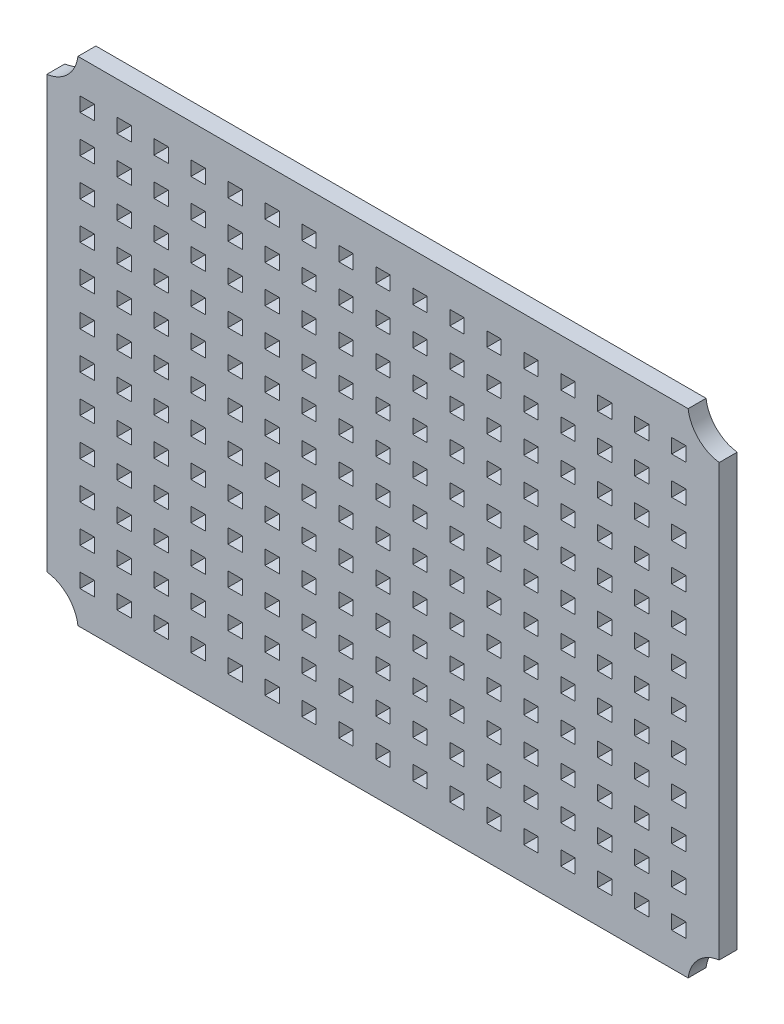
SolidWorks part; units mm, degrees
ref_plane "Plano frontal" through (0, 0, 0) normal (0, 0, 1) x (1, 0, 0)
ref_plane "Plano superior" through (0, 0, 0) normal (0, 1, 0) x (1, 0, 0)
ref_plane "Plano direito" through (0, 0, 0) normal (1, 0, 0) x (0, 0, -1)
sketch "Esboço1" plane through (0, 0, 0) normal (0, 0, 1) x (1, 0, 0)
  line L0 (-85, 70) -> (85, 70)
  line L1 (95, 60) -> (95, -60)
  line L2 (85, -70) -> (-85, -70)
  line L3 (-95, -60) -> (-95, 60)
  arc A0 (-95, 60) -> (-85, 70) centre (-95, 70) ccw
  arc A1 (85, 70) -> (95, 60) centre (95, 70) ccw
  arc A2 (95, -60) -> (85, -70) centre (95, -70) ccw
  arc A3 (-85, -70) -> (-95, -60) centre (-95, -70) ccw
extrude "Ressalto-extrusão1" add sketch "Esboço1" along normal blind 5
sketch "Esboço2" plane through (0, 0, 5) normal (0, 0, 1) x (1, 0, 0)
  line L1 (-87.9289, 62.9289) -> (87.9289, 62.9289)
  line L2 (-87.9289, 62.9289) -> (-87.9289, -62.9289)
  line L3 (-87.9289, -62.9289) -> (87.9289, -62.9289)
  line L4 (87.9289, 62.9289) -> (87.9289, -62.9289)
  line L5 (-87.9289, 62.9289) -> (87.9289, -62.9289) construction
  line L6 (-87.9289, -62.9289) -> (87.9289, 62.9289) construction
  arc A0 (95, -60) -> (85, -70) centre (95, -70) ccw construction
  point P0 (0, 0)
sketch "Esboço3" plane through (0, 0, 5) normal (0, 0, 1) x (1, 0, 0)
  line L0 (-74.1875, 55.5) -> (-70.1875, 55.5)
  line L7 (-70.1875, 59.5) -> (-70.1875, 55.5)
  line L8 (-74.1875, 59.5) -> (-70.1875, 59.5)
  line L9 (-74.1875, 59.5) -> (-74.1875, 55.5)
  line L10 (-84.5, 59.5) -> (-80.5, 59.5)
  line L11 (-84.5, 59.5) -> (-84.5, 55.5)
  line L12 (-84.5, 55.5) -> (-80.5, 55.5)
  line L13 (-80.5, 59.5) -> (-80.5, 55.5)
  line L14 (-84.5, 59.5) -> (-80.5, 55.5) construction
  line L15 (-84.5, 55.5) -> (-80.5, 59.5) construction
  line L16 (-63.875, 55.5) -> (-59.875, 55.5)
  line L17 (-59.875, 59.5) -> (-59.875, 55.5)
  line L18 (-63.875, 59.5) -> (-59.875, 59.5)
  line L19 (-63.875, 59.5) -> (-63.875, 55.5)
  line L20 (-53.5625, 55.5) -> (-49.5625, 55.5)
  line L21 (-49.5625, 59.5) -> (-49.5625, 55.5)
  line L22 (-53.5625, 59.5) -> (-49.5625, 59.5)
  line L23 (-53.5625, 59.5) -> (-53.5625, 55.5)
  line L24 (-43.25, 55.5) -> (-39.25, 55.5)
  line L25 (-39.25, 59.5) -> (-39.25, 55.5)
  line L26 (-43.25, 59.5) -> (-39.25, 59.5)
  line L27 (-43.25, 59.5) -> (-43.25, 55.5)
  line L28 (-32.9375, 55.5) -> (-28.9375, 55.5)
  line L29 (-28.9375, 59.5) -> (-28.9375, 55.5)
  line L30 (-32.9375, 59.5) -> (-28.9375, 59.5)
  line L31 (-32.9375, 59.5) -> (-32.9375, 55.5)
  line L32 (-22.625, 55.5) -> (-18.625, 55.5)
  line L33 (-18.625, 59.5) -> (-18.625, 55.5)
  line L34 (-22.625, 59.5) -> (-18.625, 59.5)
  line L35 (-22.625, 59.5) -> (-22.625, 55.5)
  line L36 (-12.3125, 55.5) -> (-8.3125, 55.5)
  line L37 (-8.3125, 59.5) -> (-8.3125, 55.5)
  line L38 (-12.3125, 59.5) -> (-8.3125, 59.5)
  line L39 (-12.3125, 59.5) -> (-12.3125, 55.5)
  line L40 (-2, 55.5) -> (2, 55.5)
  line L41 (2, 59.5) -> (2, 55.5)
  line L42 (-2, 59.5) -> (2, 59.5)
  line L43 (-2, 59.5) -> (-2, 55.5)
  line L44 (8.3125, 55.5) -> (12.3125, 55.5)
  line L45 (12.3125, 59.5) -> (12.3125, 55.5)
  line L46 (8.3125, 59.5) -> (12.3125, 59.5)
  line L47 (8.3125, 59.5) -> (8.3125, 55.5)
  line L48 (18.625, 55.5) -> (22.625, 55.5)
  line L49 (22.625, 59.5) -> (22.625, 55.5)
  line L50 (18.625, 59.5) -> (22.625, 59.5)
  line L51 (18.625, 59.5) -> (18.625, 55.5)
  line L52 (28.9375, 55.5) -> (32.9375, 55.5)
  line L53 (32.9375, 59.5) -> (32.9375, 55.5)
  line L54 (28.9375, 59.5) -> (32.9375, 59.5)
  line L55 (28.9375, 59.5) -> (28.9375, 55.5)
  line L56 (39.25, 55.5) -> (43.25, 55.5)
  line L57 (43.25, 59.5) -> (43.25, 55.5)
  line L58 (39.25, 59.5) -> (43.25, 59.5)
  line L59 (39.25, 59.5) -> (39.25, 55.5)
  line L60 (49.5625, 55.5) -> (53.5625, 55.5)
  line L61 (53.5625, 59.5) -> (53.5625, 55.5)
  line L62 (49.5625, 59.5) -> (53.5625, 59.5)
  line L63 (49.5625, 59.5) -> (49.5625, 55.5)
  line L64 (59.875, 55.5) -> (63.875, 55.5)
  line L65 (63.875, 59.5) -> (63.875, 55.5)
  line L66 (59.875, 59.5) -> (63.875, 59.5)
  line L67 (59.875, 59.5) -> (59.875, 55.5)
  line L68 (70.1875, 55.5) -> (74.1875, 55.5)
  line L69 (74.1875, 59.5) -> (74.1875, 55.5)
  line L70 (70.1875, 59.5) -> (74.1875, 59.5)
  line L71 (70.1875, 59.5) -> (70.1875, 55.5)
  line L72 (80.5, 55.5) -> (84.5, 55.5)
  line L73 (84.5, 59.5) -> (84.5, 55.5)
  line L74 (80.5, 59.5) -> (84.5, 59.5)
  line L75 (80.5, 59.5) -> (80.5, 55.5)
  line L76 (-74.1875, 45.0455) -> (-70.1875, 45.0455)
  line L77 (-70.1875, 49.0455) -> (-70.1875, 45.0455)
  line L78 (-74.1875, 49.0455) -> (-70.1875, 49.0455)
  line L79 (-74.1875, 49.0455) -> (-74.1875, 45.0455)
  line L80 (-63.875, 45.0455) -> (-59.875, 45.0455)
  line L81 (-59.875, 49.0455) -> (-59.875, 45.0455)
  line L82 (-63.875, 49.0455) -> (-59.875, 49.0455)
  line L83 (-63.875, 49.0455) -> (-63.875, 45.0455)
  line L84 (-53.5625, 45.0455) -> (-49.5625, 45.0455)
  line L85 (-49.5625, 49.0455) -> (-49.5625, 45.0455)
  line L86 (-53.5625, 49.0455) -> (-49.5625, 49.0455)
  line L87 (-53.5625, 49.0455) -> (-53.5625, 45.0455)
  line L88 (-43.25, 45.0455) -> (-39.25, 45.0455)
  line L89 (-39.25, 49.0455) -> (-39.25, 45.0455)
  line L90 (-43.25, 49.0455) -> (-39.25, 49.0455)
  line L91 (-43.25, 49.0455) -> (-43.25, 45.0455)
  line L92 (-32.9375, 45.0455) -> (-28.9375, 45.0455)
  line L93 (-28.9375, 49.0455) -> (-28.9375, 45.0455)
  line L94 (-32.9375, 49.0455) -> (-28.9375, 49.0455)
  line L95 (-32.9375, 49.0455) -> (-32.9375, 45.0455)
  line L96 (-22.625, 45.0455) -> (-18.625, 45.0455)
  line L97 (-18.625, 49.0455) -> (-18.625, 45.0455)
  line L98 (-22.625, 49.0455) -> (-18.625, 49.0455)
  line L99 (-22.625, 49.0455) -> (-22.625, 45.0455)
  line L100 (-12.3125, 45.0455) -> (-8.3125, 45.0455)
  line L101 (-8.3125, 49.0455) -> (-8.3125, 45.0455)
  line L102 (-12.3125, 49.0455) -> (-8.3125, 49.0455)
  line L103 (-12.3125, 49.0455) -> (-12.3125, 45.0455)
  line L104 (-2, 45.0455) -> (2, 45.0455)
  line L105 (2, 49.0455) -> (2, 45.0455)
  line L106 (-2, 49.0455) -> (2, 49.0455)
  line L107 (-2, 49.0455) -> (-2, 45.0455)
  line L108 (8.3125, 45.0455) -> (12.3125, 45.0455)
  line L109 (12.3125, 49.0455) -> (12.3125, 45.0455)
  line L110 (8.3125, 49.0455) -> (12.3125, 49.0455)
  line L111 (8.3125, 49.0455) -> (8.3125, 45.0455)
  line L112 (18.625, 45.0455) -> (22.625, 45.0455)
  line L113 (22.625, 49.0455) -> (22.625, 45.0455)
  line L114 (18.625, 49.0455) -> (22.625, 49.0455)
  line L115 (18.625, 49.0455) -> (18.625, 45.0455)
  line L116 (28.9375, 45.0455) -> (32.9375, 45.0455)
  line L117 (32.9375, 49.0455) -> (32.9375, 45.0455)
  line L118 (28.9375, 49.0455) -> (32.9375, 49.0455)
  line L119 (28.9375, 49.0455) -> (28.9375, 45.0455)
  line L120 (39.25, 45.0455) -> (43.25, 45.0455)
  line L121 (43.25, 49.0455) -> (43.25, 45.0455)
  line L122 (39.25, 49.0455) -> (43.25, 49.0455)
  line L123 (39.25, 49.0455) -> (39.25, 45.0455)
  line L124 (49.5625, 45.0455) -> (53.5625, 45.0455)
  line L125 (53.5625, 49.0455) -> (53.5625, 45.0455)
  line L126 (49.5625, 49.0455) -> (53.5625, 49.0455)
  line L127 (49.5625, 49.0455) -> (49.5625, 45.0455)
  line L128 (59.875, 45.0455) -> (63.875, 45.0455)
  line L129 (63.875, 49.0455) -> (63.875, 45.0455)
  line L130 (59.875, 49.0455) -> (63.875, 49.0455)
  line L131 (59.875, 49.0455) -> (59.875, 45.0455)
  line L132 (70.1875, 45.0455) -> (74.1875, 45.0455)
  line L133 (74.1875, 49.0455) -> (74.1875, 45.0455)
  line L134 (70.1875, 49.0455) -> (74.1875, 49.0455)
  line L135 (70.1875, 49.0455) -> (70.1875, 45.0455)
  line L136 (80.5, 45.0455) -> (84.5, 45.0455)
  line L137 (84.5, 49.0455) -> (84.5, 45.0455)
  line L138 (80.5, 49.0455) -> (84.5, 49.0455)
  line L139 (80.5, 49.0455) -> (80.5, 45.0455)
  line L140 (-74.1875, 34.591) -> (-70.1875, 34.591)
  line L141 (-70.1875, 38.591) -> (-70.1875, 34.591)
  line L142 (-74.1875, 38.591) -> (-70.1875, 38.591)
  line L143 (-74.1875, 38.591) -> (-74.1875, 34.591)
  line L144 (-63.875, 34.591) -> (-59.875, 34.591)
  line L145 (-59.875, 38.591) -> (-59.875, 34.591)
  line L146 (-63.875, 38.591) -> (-59.875, 38.591)
  line L147 (-63.875, 38.591) -> (-63.875, 34.591)
  line L148 (-53.5625, 34.591) -> (-49.5625, 34.591)
  line L149 (-49.5625, 38.591) -> (-49.5625, 34.591)
  line L150 (-53.5625, 38.591) -> (-49.5625, 38.591)
  line L151 (-53.5625, 38.591) -> (-53.5625, 34.591)
  line L152 (-43.25, 34.591) -> (-39.25, 34.591)
  line L153 (-39.25, 38.591) -> (-39.25, 34.591)
  line L154 (-43.25, 38.591) -> (-39.25, 38.591)
  line L155 (-43.25, 38.591) -> (-43.25, 34.591)
  line L156 (-32.9375, 34.591) -> (-28.9375, 34.591)
  line L157 (-28.9375, 38.591) -> (-28.9375, 34.591)
  line L158 (-32.9375, 38.591) -> (-28.9375, 38.591)
  line L159 (-32.9375, 38.591) -> (-32.9375, 34.591)
  line L160 (-22.625, 34.591) -> (-18.625, 34.591)
  line L161 (-18.625, 38.591) -> (-18.625, 34.591)
  line L162 (-22.625, 38.591) -> (-18.625, 38.591)
  line L163 (-22.625, 38.591) -> (-22.625, 34.591)
  line L164 (-12.3125, 34.591) -> (-8.3125, 34.591)
  line L165 (-8.3125, 38.591) -> (-8.3125, 34.591)
  line L166 (-12.3125, 38.591) -> (-8.3125, 38.591)
  line L167 (-12.3125, 38.591) -> (-12.3125, 34.591)
  line L168 (-2, 34.591) -> (2, 34.591)
  line L169 (2, 38.591) -> (2, 34.591)
  line L170 (-2, 38.591) -> (2, 38.591)
  line L171 (-2, 38.591) -> (-2, 34.591)
  line L172 (8.3125, 34.591) -> (12.3125, 34.591)
  line L173 (12.3125, 38.591) -> (12.3125, 34.591)
  line L174 (8.3125, 38.591) -> (12.3125, 38.591)
  line L175 (8.3125, 38.591) -> (8.3125, 34.591)
  line L176 (18.625, 34.591) -> (22.625, 34.591)
  line L177 (22.625, 38.591) -> (22.625, 34.591)
  line L178 (18.625, 38.591) -> (22.625, 38.591)
  line L179 (18.625, 38.591) -> (18.625, 34.591)
  line L180 (28.9375, 34.591) -> (32.9375, 34.591)
  line L181 (32.9375, 38.591) -> (32.9375, 34.591)
  line L182 (28.9375, 38.591) -> (32.9375, 38.591)
  line L183 (28.9375, 38.591) -> (28.9375, 34.591)
  line L184 (39.25, 34.591) -> (43.25, 34.591)
  line L185 (43.25, 38.591) -> (43.25, 34.591)
  line L186 (39.25, 38.591) -> (43.25, 38.591)
  line L187 (39.25, 38.591) -> (39.25, 34.591)
  line L188 (49.5625, 34.591) -> (53.5625, 34.591)
  line L189 (53.5625, 38.591) -> (53.5625, 34.591)
  line L190 (49.5625, 38.591) -> (53.5625, 38.591)
  line L191 (49.5625, 38.591) -> (49.5625, 34.591)
  line L192 (59.875, 34.591) -> (63.875, 34.591)
  line L193 (63.875, 38.591) -> (63.875, 34.591)
  line L194 (59.875, 38.591) -> (63.875, 38.591)
  line L195 (59.875, 38.591) -> (59.875, 34.591)
  line L196 (70.1875, 34.591) -> (74.1875, 34.591)
  line L197 (74.1875, 38.591) -> (74.1875, 34.591)
  line L198 (70.1875, 38.591) -> (74.1875, 38.591)
  line L199 (70.1875, 38.591) -> (70.1875, 34.591)
  line L200 (80.5, 34.591) -> (84.5, 34.591)
  line L201 (84.5, 38.591) -> (84.5, 34.591)
  line L202 (80.5, 38.591) -> (84.5, 38.591)
  line L203 (80.5, 38.591) -> (80.5, 34.591)
  line L204 (-74.1875, 24.1365) -> (-70.1875, 24.1365)
  line L205 (-70.1875, 28.1365) -> (-70.1875, 24.1365)
  line L206 (-74.1875, 28.1365) -> (-70.1875, 28.1365)
  line L207 (-74.1875, 28.1365) -> (-74.1875, 24.1365)
  line L208 (-63.875, 24.1365) -> (-59.875, 24.1365)
  line L209 (-59.875, 28.1365) -> (-59.875, 24.1365)
  line L210 (-63.875, 28.1365) -> (-59.875, 28.1365)
  line L211 (-63.875, 28.1365) -> (-63.875, 24.1365)
  line L212 (-53.5625, 24.1365) -> (-49.5625, 24.1365)
  line L213 (-49.5625, 28.1365) -> (-49.5625, 24.1365)
  line L214 (-53.5625, 28.1365) -> (-49.5625, 28.1365)
  line L215 (-53.5625, 28.1365) -> (-53.5625, 24.1365)
  line L216 (-43.25, 24.1365) -> (-39.25, 24.1365)
  line L217 (-39.25, 28.1365) -> (-39.25, 24.1365)
  line L218 (-43.25, 28.1365) -> (-39.25, 28.1365)
  line L219 (-43.25, 28.1365) -> (-43.25, 24.1365)
  line L220 (-32.9375, 24.1365) -> (-28.9375, 24.1365)
  line L221 (-28.9375, 28.1365) -> (-28.9375, 24.1365)
  line L222 (-32.9375, 28.1365) -> (-28.9375, 28.1365)
  line L223 (-32.9375, 28.1365) -> (-32.9375, 24.1365)
  line L224 (-22.625, 24.1365) -> (-18.625, 24.1365)
  line L225 (-18.625, 28.1365) -> (-18.625, 24.1365)
  line L226 (-22.625, 28.1365) -> (-18.625, 28.1365)
  line L227 (-22.625, 28.1365) -> (-22.625, 24.1365)
  line L228 (-12.3125, 24.1365) -> (-8.3125, 24.1365)
  line L229 (-8.3125, 28.1365) -> (-8.3125, 24.1365)
  line L230 (-12.3125, 28.1365) -> (-8.3125, 28.1365)
  line L231 (-12.3125, 28.1365) -> (-12.3125, 24.1365)
  line L232 (-2, 24.1365) -> (2, 24.1365)
  line L233 (2, 28.1365) -> (2, 24.1365)
  line L234 (-2, 28.1365) -> (2, 28.1365)
  line L235 (-2, 28.1365) -> (-2, 24.1365)
  line L236 (8.3125, 24.1365) -> (12.3125, 24.1365)
  line L237 (12.3125, 28.1365) -> (12.3125, 24.1365)
  line L238 (8.3125, 28.1365) -> (12.3125, 28.1365)
  line L239 (8.3125, 28.1365) -> (8.3125, 24.1365)
  line L240 (18.625, 24.1365) -> (22.625, 24.1365)
  line L241 (22.625, 28.1365) -> (22.625, 24.1365)
  line L242 (18.625, 28.1365) -> (22.625, 28.1365)
  line L243 (18.625, 28.1365) -> (18.625, 24.1365)
  line L244 (28.9375, 24.1365) -> (32.9375, 24.1365)
  line L245 (32.9375, 28.1365) -> (32.9375, 24.1365)
  line L246 (28.9375, 28.1365) -> (32.9375, 28.1365)
  line L247 (28.9375, 28.1365) -> (28.9375, 24.1365)
  line L248 (39.25, 24.1365) -> (43.25, 24.1365)
  line L249 (43.25, 28.1365) -> (43.25, 24.1365)
  line L250 (39.25, 28.1365) -> (43.25, 28.1365)
  line L251 (39.25, 28.1365) -> (39.25, 24.1365)
  line L252 (49.5625, 24.1365) -> (53.5625, 24.1365)
  line L253 (53.5625, 28.1365) -> (53.5625, 24.1365)
  line L254 (49.5625, 28.1365) -> (53.5625, 28.1365)
  line L255 (49.5625, 28.1365) -> (49.5625, 24.1365)
  line L256 (59.875, 24.1365) -> (63.875, 24.1365)
  line L257 (63.875, 28.1365) -> (63.875, 24.1365)
  line L258 (59.875, 28.1365) -> (63.875, 28.1365)
  line L259 (59.875, 28.1365) -> (59.875, 24.1365)
  line L260 (70.1875, 24.1365) -> (74.1875, 24.1365)
  line L261 (74.1875, 28.1365) -> (74.1875, 24.1365)
  line L262 (70.1875, 28.1365) -> (74.1875, 28.1365)
  line L263 (70.1875, 28.1365) -> (70.1875, 24.1365)
  line L264 (80.5, 24.1365) -> (84.5, 24.1365)
  line L265 (84.5, 28.1365) -> (84.5, 24.1365)
  line L266 (80.5, 28.1365) -> (84.5, 28.1365)
  line L267 (80.5, 28.1365) -> (80.5, 24.1365)
  line L268 (-74.1875, 13.682) -> (-70.1875, 13.682)
  line L269 (-70.1875, 17.682) -> (-70.1875, 13.682)
  line L270 (-74.1875, 17.682) -> (-70.1875, 17.682)
  line L271 (-74.1875, 17.682) -> (-74.1875, 13.682)
  line L272 (-63.875, 13.682) -> (-59.875, 13.682)
  line L273 (-59.875, 17.682) -> (-59.875, 13.682)
  line L274 (-63.875, 17.682) -> (-59.875, 17.682)
  line L275 (-63.875, 17.682) -> (-63.875, 13.682)
  line L276 (-53.5625, 13.682) -> (-49.5625, 13.682)
  line L277 (-49.5625, 17.682) -> (-49.5625, 13.682)
  line L278 (-53.5625, 17.682) -> (-49.5625, 17.682)
  line L279 (-53.5625, 17.682) -> (-53.5625, 13.682)
  line L280 (-43.25, 13.682) -> (-39.25, 13.682)
  line L281 (-39.25, 17.682) -> (-39.25, 13.682)
  line L282 (-43.25, 17.682) -> (-39.25, 17.682)
  line L283 (-43.25, 17.682) -> (-43.25, 13.682)
  line L284 (-32.9375, 13.682) -> (-28.9375, 13.682)
  line L285 (-28.9375, 17.682) -> (-28.9375, 13.682)
  line L286 (-32.9375, 17.682) -> (-28.9375, 17.682)
  line L287 (-32.9375, 17.682) -> (-32.9375, 13.682)
  line L288 (-22.625, 13.682) -> (-18.625, 13.682)
  line L289 (-18.625, 17.682) -> (-18.625, 13.682)
  line L290 (-22.625, 17.682) -> (-18.625, 17.682)
  line L291 (-22.625, 17.682) -> (-22.625, 13.682)
  line L292 (-12.3125, 13.682) -> (-8.3125, 13.682)
  line L293 (-8.3125, 17.682) -> (-8.3125, 13.682)
  line L294 (-12.3125, 17.682) -> (-8.3125, 17.682)
  line L295 (-12.3125, 17.682) -> (-12.3125, 13.682)
  line L296 (-2, 13.682) -> (2, 13.682)
  line L297 (2, 17.682) -> (2, 13.682)
  line L298 (-2, 17.682) -> (2, 17.682)
  line L299 (-2, 17.682) -> (-2, 13.682)
  line L300 (8.3125, 13.682) -> (12.3125, 13.682)
  line L301 (12.3125, 17.682) -> (12.3125, 13.682)
  line L302 (8.3125, 17.682) -> (12.3125, 17.682)
  line L303 (8.3125, 17.682) -> (8.3125, 13.682)
  line L304 (18.625, 13.682) -> (22.625, 13.682)
  line L305 (22.625, 17.682) -> (22.625, 13.682)
  line L306 (18.625, 17.682) -> (22.625, 17.682)
  line L307 (18.625, 17.682) -> (18.625, 13.682)
  line L308 (28.9375, 13.682) -> (32.9375, 13.682)
  line L309 (32.9375, 17.682) -> (32.9375, 13.682)
  line L310 (28.9375, 17.682) -> (32.9375, 17.682)
  line L311 (28.9375, 17.682) -> (28.9375, 13.682)
  line L312 (39.25, 13.682) -> (43.25, 13.682)
  line L313 (43.25, 17.682) -> (43.25, 13.682)
  line L314 (39.25, 17.682) -> (43.25, 17.682)
  line L315 (39.25, 17.682) -> (39.25, 13.682)
  line L316 (49.5625, 13.682) -> (53.5625, 13.682)
  line L317 (53.5625, 17.682) -> (53.5625, 13.682)
  line L318 (49.5625, 17.682) -> (53.5625, 17.682)
  line L319 (49.5625, 17.682) -> (49.5625, 13.682)
  line L320 (59.875, 13.682) -> (63.875, 13.682)
  line L321 (63.875, 17.682) -> (63.875, 13.682)
  line L322 (59.875, 17.682) -> (63.875, 17.682)
  line L323 (59.875, 17.682) -> (59.875, 13.682)
  line L324 (70.1875, 13.682) -> (74.1875, 13.682)
  line L325 (74.1875, 17.682) -> (74.1875, 13.682)
  line L326 (70.1875, 17.682) -> (74.1875, 17.682)
  line L327 (70.1875, 17.682) -> (70.1875, 13.682)
  line L328 (80.5, 13.682) -> (84.5, 13.682)
  line L329 (84.5, 17.682) -> (84.5, 13.682)
  line L330 (80.5, 17.682) -> (84.5, 17.682)
  line L331 (80.5, 17.682) -> (80.5, 13.682)
  line L332 (-74.1875, 3.2275) -> (-70.1875, 3.2275)
  line L333 (-70.1875, 7.2275) -> (-70.1875, 3.2275)
  line L334 (-74.1875, 7.2275) -> (-70.1875, 7.2275)
  line L335 (-74.1875, 7.2275) -> (-74.1875, 3.2275)
  line L336 (-63.875, 3.2275) -> (-59.875, 3.2275)
  line L337 (-59.875, 7.2275) -> (-59.875, 3.2275)
  line L338 (-63.875, 7.2275) -> (-59.875, 7.2275)
  line L339 (-63.875, 7.2275) -> (-63.875, 3.2275)
  line L340 (-53.5625, 3.2275) -> (-49.5625, 3.2275)
  line L341 (-49.5625, 7.2275) -> (-49.5625, 3.2275)
  line L342 (-53.5625, 7.2275) -> (-49.5625, 7.2275)
  line L343 (-53.5625, 7.2275) -> (-53.5625, 3.2275)
  line L344 (-43.25, 3.2275) -> (-39.25, 3.2275)
  line L345 (-39.25, 7.2275) -> (-39.25, 3.2275)
  line L346 (-43.25, 7.2275) -> (-39.25, 7.2275)
  line L347 (-43.25, 7.2275) -> (-43.25, 3.2275)
  line L348 (-32.9375, 3.2275) -> (-28.9375, 3.2275)
  line L349 (-28.9375, 7.2275) -> (-28.9375, 3.2275)
  line L350 (-32.9375, 7.2275) -> (-28.9375, 7.2275)
  line L351 (-32.9375, 7.2275) -> (-32.9375, 3.2275)
  line L352 (-22.625, 3.2275) -> (-18.625, 3.2275)
  line L353 (-18.625, 7.2275) -> (-18.625, 3.2275)
  line L354 (-22.625, 7.2275) -> (-18.625, 7.2275)
  line L355 (-22.625, 7.2275) -> (-22.625, 3.2275)
  line L356 (-12.3125, 3.2275) -> (-8.3125, 3.2275)
  line L357 (-8.3125, 7.2275) -> (-8.3125, 3.2275)
  line L358 (-12.3125, 7.2275) -> (-8.3125, 7.2275)
  line L359 (-12.3125, 7.2275) -> (-12.3125, 3.2275)
  line L360 (-2, 3.2275) -> (2, 3.2275)
  line L361 (2, 7.2275) -> (2, 3.2275)
  line L362 (-2, 7.2275) -> (2, 7.2275)
  line L363 (-2, 7.2275) -> (-2, 3.2275)
  line L364 (8.3125, 3.2275) -> (12.3125, 3.2275)
  line L365 (12.3125, 7.2275) -> (12.3125, 3.2275)
  line L366 (8.3125, 7.2275) -> (12.3125, 7.2275)
  line L367 (8.3125, 7.2275) -> (8.3125, 3.2275)
  line L368 (18.625, 3.2275) -> (22.625, 3.2275)
  line L369 (22.625, 7.2275) -> (22.625, 3.2275)
  line L370 (18.625, 7.2275) -> (22.625, 7.2275)
  line L371 (18.625, 7.2275) -> (18.625, 3.2275)
  line L372 (28.9375, 3.2275) -> (32.9375, 3.2275)
  line L373 (32.9375, 7.2275) -> (32.9375, 3.2275)
  line L374 (28.9375, 7.2275) -> (32.9375, 7.2275)
  line L375 (28.9375, 7.2275) -> (28.9375, 3.2275)
  line L376 (39.25, 3.2275) -> (43.25, 3.2275)
  line L377 (43.25, 7.2275) -> (43.25, 3.2275)
  line L378 (39.25, 7.2275) -> (43.25, 7.2275)
  line L379 (39.25, 7.2275) -> (39.25, 3.2275)
  line L380 (49.5625, 3.2275) -> (53.5625, 3.2275)
  line L381 (53.5625, 7.2275) -> (53.5625, 3.2275)
  line L382 (49.5625, 7.2275) -> (53.5625, 7.2275)
  line L383 (49.5625, 7.2275) -> (49.5625, 3.2275)
  line L384 (59.875, 3.2275) -> (63.875, 3.2275)
  line L385 (63.875, 7.2275) -> (63.875, 3.2275)
  line L386 (59.875, 7.2275) -> (63.875, 7.2275)
  line L387 (59.875, 7.2275) -> (59.875, 3.2275)
  line L388 (70.1875, 3.2275) -> (74.1875, 3.2275)
  line L389 (74.1875, 7.2275) -> (74.1875, 3.2275)
  line L390 (70.1875, 7.2275) -> (74.1875, 7.2275)
  line L391 (70.1875, 7.2275) -> (70.1875, 3.2275)
  line L392 (80.5, 3.2275) -> (84.5, 3.2275)
  line L393 (84.5, 7.2275) -> (84.5, 3.2275)
  line L394 (80.5, 7.2275) -> (84.5, 7.2275)
  line L395 (80.5, 7.2275) -> (80.5, 3.2275)
  line L396 (-74.1875, -7.227) -> (-70.1875, -7.227)
  line L397 (-70.1875, -3.227) -> (-70.1875, -7.227)
  line L398 (-74.1875, -3.227) -> (-70.1875, -3.227)
  line L399 (-74.1875, -3.227) -> (-74.1875, -7.227)
  line L400 (-63.875, -7.227) -> (-59.875, -7.227)
  line L401 (-59.875, -3.227) -> (-59.875, -7.227)
  line L402 (-63.875, -3.227) -> (-59.875, -3.227)
  line L403 (-63.875, -3.227) -> (-63.875, -7.227)
  line L404 (-53.5625, -7.227) -> (-49.5625, -7.227)
  line L405 (-49.5625, -3.227) -> (-49.5625, -7.227)
  line L406 (-53.5625, -3.227) -> (-49.5625, -3.227)
  line L407 (-53.5625, -3.227) -> (-53.5625, -7.227)
  line L408 (-43.25, -7.227) -> (-39.25, -7.227)
  line L409 (-39.25, -3.227) -> (-39.25, -7.227)
  line L410 (-43.25, -3.227) -> (-39.25, -3.227)
  line L411 (-43.25, -3.227) -> (-43.25, -7.227)
  line L412 (-32.9375, -7.227) -> (-28.9375, -7.227)
  line L413 (-28.9375, -3.227) -> (-28.9375, -7.227)
  line L414 (-32.9375, -3.227) -> (-28.9375, -3.227)
  line L415 (-32.9375, -3.227) -> (-32.9375, -7.227)
  line L416 (-22.625, -7.227) -> (-18.625, -7.227)
  line L417 (-18.625, -3.227) -> (-18.625, -7.227)
  line L418 (-22.625, -3.227) -> (-18.625, -3.227)
  line L419 (-22.625, -3.227) -> (-22.625, -7.227)
  line L420 (-12.3125, -7.227) -> (-8.3125, -7.227)
  line L421 (-8.3125, -3.227) -> (-8.3125, -7.227)
  line L422 (-12.3125, -3.227) -> (-8.3125, -3.227)
  line L423 (-12.3125, -3.227) -> (-12.3125, -7.227)
  line L424 (-2, -7.227) -> (2, -7.227)
  line L425 (2, -3.227) -> (2, -7.227)
  line L426 (-2, -3.227) -> (2, -3.227)
  line L427 (-2, -3.227) -> (-2, -7.227)
  line L428 (8.3125, -7.227) -> (12.3125, -7.227)
  line L429 (12.3125, -3.227) -> (12.3125, -7.227)
  line L430 (8.3125, -3.227) -> (12.3125, -3.227)
  line L431 (8.3125, -3.227) -> (8.3125, -7.227)
  line L432 (18.625, -7.227) -> (22.625, -7.227)
  line L433 (22.625, -3.227) -> (22.625, -7.227)
  line L434 (18.625, -3.227) -> (22.625, -3.227)
  line L435 (18.625, -3.227) -> (18.625, -7.227)
  line L436 (28.9375, -7.227) -> (32.9375, -7.227)
  line L437 (32.9375, -3.227) -> (32.9375, -7.227)
  line L438 (28.9375, -3.227) -> (32.9375, -3.227)
  line L439 (28.9375, -3.227) -> (28.9375, -7.227)
  line L440 (39.25, -7.227) -> (43.25, -7.227)
  line L441 (43.25, -3.227) -> (43.25, -7.227)
  line L442 (39.25, -3.227) -> (43.25, -3.227)
  line L443 (39.25, -3.227) -> (39.25, -7.227)
  line L444 (49.5625, -7.227) -> (53.5625, -7.227)
  line L445 (53.5625, -3.227) -> (53.5625, -7.227)
  line L446 (49.5625, -3.227) -> (53.5625, -3.227)
  line L447 (49.5625, -3.227) -> (49.5625, -7.227)
  line L448 (59.875, -7.227) -> (63.875, -7.227)
  line L449 (63.875, -3.227) -> (63.875, -7.227)
  line L450 (59.875, -3.227) -> (63.875, -3.227)
  line L451 (59.875, -3.227) -> (59.875, -7.227)
  line L452 (70.1875, -7.227) -> (74.1875, -7.227)
  line L453 (74.1875, -3.227) -> (74.1875, -7.227)
  line L454 (70.1875, -3.227) -> (74.1875, -3.227)
  line L455 (70.1875, -3.227) -> (70.1875, -7.227)
  line L456 (80.5, -7.227) -> (84.5, -7.227)
  line L457 (84.5, -3.227) -> (84.5, -7.227)
  line L458 (80.5, -3.227) -> (84.5, -3.227)
  line L459 (80.5, -3.227) -> (80.5, -7.227)
  line L460 (-74.1875, -17.6815) -> (-70.1875, -17.6815)
  line L461 (-70.1875, -13.6815) -> (-70.1875, -17.6815)
  line L462 (-74.1875, -13.6815) -> (-70.1875, -13.6815)
  line L463 (-74.1875, -13.6815) -> (-74.1875, -17.6815)
  line L464 (-63.875, -17.6815) -> (-59.875, -17.6815)
  line L465 (-59.875, -13.6815) -> (-59.875, -17.6815)
  line L466 (-63.875, -13.6815) -> (-59.875, -13.6815)
  line L467 (-63.875, -13.6815) -> (-63.875, -17.6815)
  line L468 (-53.5625, -17.6815) -> (-49.5625, -17.6815)
  line L469 (-49.5625, -13.6815) -> (-49.5625, -17.6815)
  line L470 (-53.5625, -13.6815) -> (-49.5625, -13.6815)
  line L471 (-53.5625, -13.6815) -> (-53.5625, -17.6815)
  line L472 (-43.25, -17.6815) -> (-39.25, -17.6815)
  line L473 (-39.25, -13.6815) -> (-39.25, -17.6815)
  line L474 (-43.25, -13.6815) -> (-39.25, -13.6815)
  line L475 (-43.25, -13.6815) -> (-43.25, -17.6815)
  line L476 (-32.9375, -17.6815) -> (-28.9375, -17.6815)
  line L477 (-28.9375, -13.6815) -> (-28.9375, -17.6815)
  line L478 (-32.9375, -13.6815) -> (-28.9375, -13.6815)
  line L479 (-32.9375, -13.6815) -> (-32.9375, -17.6815)
  line L480 (-22.625, -17.6815) -> (-18.625, -17.6815)
  line L481 (-18.625, -13.6815) -> (-18.625, -17.6815)
  line L482 (-22.625, -13.6815) -> (-18.625, -13.6815)
  line L483 (-22.625, -13.6815) -> (-22.625, -17.6815)
  line L484 (-12.3125, -17.6815) -> (-8.3125, -17.6815)
  line L485 (-8.3125, -13.6815) -> (-8.3125, -17.6815)
  line L486 (-12.3125, -13.6815) -> (-8.3125, -13.6815)
  line L487 (-12.3125, -13.6815) -> (-12.3125, -17.6815)
  line L488 (-2, -17.6815) -> (2, -17.6815)
  line L489 (2, -13.6815) -> (2, -17.6815)
  line L490 (-2, -13.6815) -> (2, -13.6815)
  line L491 (-2, -13.6815) -> (-2, -17.6815)
  line L492 (8.3125, -17.6815) -> (12.3125, -17.6815)
  line L493 (12.3125, -13.6815) -> (12.3125, -17.6815)
  line L494 (8.3125, -13.6815) -> (12.3125, -13.6815)
  line L495 (8.3125, -13.6815) -> (8.3125, -17.6815)
  line L496 (18.625, -17.6815) -> (22.625, -17.6815)
  line L497 (22.625, -13.6815) -> (22.625, -17.6815)
  line L498 (18.625, -13.6815) -> (22.625, -13.6815)
  line L499 (18.625, -13.6815) -> (18.625, -17.6815)
  line L500 (28.9375, -17.6815) -> (32.9375, -17.6815)
  line L501 (32.9375, -13.6815) -> (32.9375, -17.6815)
  line L502 (28.9375, -13.6815) -> (32.9375, -13.6815)
  line L503 (28.9375, -13.6815) -> (28.9375, -17.6815)
  line L504 (39.25, -17.6815) -> (43.25, -17.6815)
  line L505 (43.25, -13.6815) -> (43.25, -17.6815)
  line L506 (39.25, -13.6815) -> (43.25, -13.6815)
  line L507 (39.25, -13.6815) -> (39.25, -17.6815)
  line L508 (49.5625, -17.6815) -> (53.5625, -17.6815)
  line L509 (53.5625, -13.6815) -> (53.5625, -17.6815)
  line L510 (49.5625, -13.6815) -> (53.5625, -13.6815)
  line L511 (49.5625, -13.6815) -> (49.5625, -17.6815)
  line L512 (59.875, -17.6815) -> (63.875, -17.6815)
  line L513 (63.875, -13.6815) -> (63.875, -17.6815)
  line L514 (59.875, -13.6815) -> (63.875, -13.6815)
  line L515 (59.875, -13.6815) -> (59.875, -17.6815)
  line L516 (70.1875, -17.6815) -> (74.1875, -17.6815)
  line L517 (74.1875, -13.6815) -> (74.1875, -17.6815)
  line L518 (70.1875, -13.6815) -> (74.1875, -13.6815)
  line L519 (70.1875, -13.6815) -> (70.1875, -17.6815)
  line L520 (80.5, -17.6815) -> (84.5, -17.6815)
  line L521 (84.5, -13.6815) -> (84.5, -17.6815)
  line L522 (80.5, -13.6815) -> (84.5, -13.6815)
  line L523 (80.5, -13.6815) -> (80.5, -17.6815)
  line L524 (-74.1875, -28.136) -> (-70.1875, -28.136)
  line L525 (-70.1875, -24.136) -> (-70.1875, -28.136)
  line L526 (-74.1875, -24.136) -> (-70.1875, -24.136)
  line L527 (-74.1875, -24.136) -> (-74.1875, -28.136)
  line L528 (-63.875, -28.136) -> (-59.875, -28.136)
  line L529 (-59.875, -24.136) -> (-59.875, -28.136)
  line L530 (-63.875, -24.136) -> (-59.875, -24.136)
  line L531 (-63.875, -24.136) -> (-63.875, -28.136)
  line L532 (-53.5625, -28.136) -> (-49.5625, -28.136)
  line L533 (-49.5625, -24.136) -> (-49.5625, -28.136)
  line L534 (-53.5625, -24.136) -> (-49.5625, -24.136)
  line L535 (-53.5625, -24.136) -> (-53.5625, -28.136)
  line L536 (-43.25, -28.136) -> (-39.25, -28.136)
  line L537 (-39.25, -24.136) -> (-39.25, -28.136)
  line L538 (-43.25, -24.136) -> (-39.25, -24.136)
  line L539 (-43.25, -24.136) -> (-43.25, -28.136)
  line L540 (-32.9375, -28.136) -> (-28.9375, -28.136)
  line L541 (-28.9375, -24.136) -> (-28.9375, -28.136)
  line L542 (-32.9375, -24.136) -> (-28.9375, -24.136)
  line L543 (-32.9375, -24.136) -> (-32.9375, -28.136)
  line L544 (-22.625, -28.136) -> (-18.625, -28.136)
  line L545 (-18.625, -24.136) -> (-18.625, -28.136)
  line L546 (-22.625, -24.136) -> (-18.625, -24.136)
  line L547 (-22.625, -24.136) -> (-22.625, -28.136)
  line L548 (-12.3125, -28.136) -> (-8.3125, -28.136)
  line L549 (-8.3125, -24.136) -> (-8.3125, -28.136)
  line L550 (-12.3125, -24.136) -> (-8.3125, -24.136)
  line L551 (-12.3125, -24.136) -> (-12.3125, -28.136)
  line L552 (-2, -28.136) -> (2, -28.136)
  line L553 (2, -24.136) -> (2, -28.136)
  line L554 (-2, -24.136) -> (2, -24.136)
  line L555 (-2, -24.136) -> (-2, -28.136)
  line L556 (8.3125, -28.136) -> (12.3125, -28.136)
  line L557 (12.3125, -24.136) -> (12.3125, -28.136)
  line L558 (8.3125, -24.136) -> (12.3125, -24.136)
  line L559 (8.3125, -24.136) -> (8.3125, -28.136)
  line L560 (18.625, -28.136) -> (22.625, -28.136)
  line L561 (22.625, -24.136) -> (22.625, -28.136)
  line L562 (18.625, -24.136) -> (22.625, -24.136)
  line L563 (18.625, -24.136) -> (18.625, -28.136)
  line L564 (28.9375, -28.136) -> (32.9375, -28.136)
  line L565 (32.9375, -24.136) -> (32.9375, -28.136)
  line L566 (28.9375, -24.136) -> (32.9375, -24.136)
  line L567 (28.9375, -24.136) -> (28.9375, -28.136)
  line L568 (39.25, -28.136) -> (43.25, -28.136)
  line L569 (43.25, -24.136) -> (43.25, -28.136)
  line L570 (39.25, -24.136) -> (43.25, -24.136)
  line L571 (39.25, -24.136) -> (39.25, -28.136)
  line L572 (49.5625, -28.136) -> (53.5625, -28.136)
  line L573 (53.5625, -24.136) -> (53.5625, -28.136)
  line L574 (49.5625, -24.136) -> (53.5625, -24.136)
  line L575 (49.5625, -24.136) -> (49.5625, -28.136)
  line L576 (59.875, -28.136) -> (63.875, -28.136)
  line L577 (63.875, -24.136) -> (63.875, -28.136)
  line L578 (59.875, -24.136) -> (63.875, -24.136)
  line L579 (59.875, -24.136) -> (59.875, -28.136)
  line L580 (70.1875, -28.136) -> (74.1875, -28.136)
  line L581 (74.1875, -24.136) -> (74.1875, -28.136)
  line L582 (70.1875, -24.136) -> (74.1875, -24.136)
  line L583 (70.1875, -24.136) -> (70.1875, -28.136)
  line L584 (80.5, -28.136) -> (84.5, -28.136)
  line L585 (84.5, -24.136) -> (84.5, -28.136)
  line L586 (80.5, -24.136) -> (84.5, -24.136)
  line L587 (80.5, -24.136) -> (80.5, -28.136)
  line L588 (-74.1875, -38.5905) -> (-70.1875, -38.5905)
  line L589 (-70.1875, -34.5905) -> (-70.1875, -38.5905)
  line L590 (-74.1875, -34.5905) -> (-70.1875, -34.5905)
  line L591 (-74.1875, -34.5905) -> (-74.1875, -38.5905)
  line L592 (-63.875, -38.5905) -> (-59.875, -38.5905)
  line L593 (-59.875, -34.5905) -> (-59.875, -38.5905)
  line L594 (-63.875, -34.5905) -> (-59.875, -34.5905)
  line L595 (-63.875, -34.5905) -> (-63.875, -38.5905)
  line L596 (-53.5625, -38.5905) -> (-49.5625, -38.5905)
  line L597 (-49.5625, -34.5905) -> (-49.5625, -38.5905)
  line L598 (-53.5625, -34.5905) -> (-49.5625, -34.5905)
  line L599 (-53.5625, -34.5905) -> (-53.5625, -38.5905)
  line L600 (-43.25, -38.5905) -> (-39.25, -38.5905)
  line L601 (-39.25, -34.5905) -> (-39.25, -38.5905)
  line L602 (-43.25, -34.5905) -> (-39.25, -34.5905)
  line L603 (-43.25, -34.5905) -> (-43.25, -38.5905)
  line L604 (-32.9375, -38.5905) -> (-28.9375, -38.5905)
  line L605 (-28.9375, -34.5905) -> (-28.9375, -38.5905)
  line L606 (-32.9375, -34.5905) -> (-28.9375, -34.5905)
  line L607 (-32.9375, -34.5905) -> (-32.9375, -38.5905)
  line L608 (-22.625, -38.5905) -> (-18.625, -38.5905)
  line L609 (-18.625, -34.5905) -> (-18.625, -38.5905)
  line L610 (-22.625, -34.5905) -> (-18.625, -34.5905)
  line L611 (-22.625, -34.5905) -> (-22.625, -38.5905)
  line L612 (-12.3125, -38.5905) -> (-8.3125, -38.5905)
  line L613 (-8.3125, -34.5905) -> (-8.3125, -38.5905)
  line L614 (-12.3125, -34.5905) -> (-8.3125, -34.5905)
  line L615 (-12.3125, -34.5905) -> (-12.3125, -38.5905)
  line L616 (-2, -38.5905) -> (2, -38.5905)
  line L617 (2, -34.5905) -> (2, -38.5905)
  line L618 (-2, -34.5905) -> (2, -34.5905)
  line L619 (-2, -34.5905) -> (-2, -38.5905)
  line L620 (8.3125, -38.5905) -> (12.3125, -38.5905)
  line L621 (12.3125, -34.5905) -> (12.3125, -38.5905)
  line L622 (8.3125, -34.5905) -> (12.3125, -34.5905)
  line L623 (8.3125, -34.5905) -> (8.3125, -38.5905)
  line L624 (18.625, -38.5905) -> (22.625, -38.5905)
  line L625 (22.625, -34.5905) -> (22.625, -38.5905)
  line L626 (18.625, -34.5905) -> (22.625, -34.5905)
  line L627 (18.625, -34.5905) -> (18.625, -38.5905)
  line L628 (28.9375, -38.5905) -> (32.9375, -38.5905)
  line L629 (32.9375, -34.5905) -> (32.9375, -38.5905)
  line L630 (28.9375, -34.5905) -> (32.9375, -34.5905)
  line L631 (28.9375, -34.5905) -> (28.9375, -38.5905)
  line L632 (39.25, -38.5905) -> (43.25, -38.5905)
  line L633 (43.25, -34.5905) -> (43.25, -38.5905)
  line L634 (39.25, -34.5905) -> (43.25, -34.5905)
  line L635 (39.25, -34.5905) -> (39.25, -38.5905)
  line L636 (49.5625, -38.5905) -> (53.5625, -38.5905)
  line L637 (53.5625, -34.5905) -> (53.5625, -38.5905)
  line L638 (49.5625, -34.5905) -> (53.5625, -34.5905)
  line L639 (49.5625, -34.5905) -> (49.5625, -38.5905)
  line L640 (59.875, -38.5905) -> (63.875, -38.5905)
  line L641 (63.875, -34.5905) -> (63.875, -38.5905)
  line L642 (59.875, -34.5905) -> (63.875, -34.5905)
  line L643 (59.875, -34.5905) -> (59.875, -38.5905)
  line L644 (70.1875, -38.5905) -> (74.1875, -38.5905)
  line L645 (74.1875, -34.5905) -> (74.1875, -38.5905)
  line L646 (70.1875, -34.5905) -> (74.1875, -34.5905)
  line L647 (70.1875, -34.5905) -> (70.1875, -38.5905)
  line L648 (80.5, -38.5905) -> (84.5, -38.5905)
  line L649 (84.5, -34.5905) -> (84.5, -38.5905)
  line L650 (80.5, -34.5905) -> (84.5, -34.5905)
  line L651 (80.5, -34.5905) -> (80.5, -38.5905)
  line L652 (-74.1875, -49.045) -> (-70.1875, -49.045)
  line L653 (-70.1875, -45.045) -> (-70.1875, -49.045)
  line L654 (-74.1875, -45.045) -> (-70.1875, -45.045)
  line L655 (-74.1875, -45.045) -> (-74.1875, -49.045)
  line L656 (-63.875, -49.045) -> (-59.875, -49.045)
  line L657 (-59.875, -45.045) -> (-59.875, -49.045)
  line L658 (-63.875, -45.045) -> (-59.875, -45.045)
  line L659 (-63.875, -45.045) -> (-63.875, -49.045)
  line L660 (-53.5625, -49.045) -> (-49.5625, -49.045)
  line L661 (-49.5625, -45.045) -> (-49.5625, -49.045)
  line L662 (-53.5625, -45.045) -> (-49.5625, -45.045)
  line L663 (-53.5625, -45.045) -> (-53.5625, -49.045)
  line L664 (-43.25, -49.045) -> (-39.25, -49.045)
  line L665 (-39.25, -45.045) -> (-39.25, -49.045)
  line L666 (-43.25, -45.045) -> (-39.25, -45.045)
  line L667 (-43.25, -45.045) -> (-43.25, -49.045)
  line L668 (-32.9375, -49.045) -> (-28.9375, -49.045)
  line L669 (-28.9375, -45.045) -> (-28.9375, -49.045)
  line L670 (-32.9375, -45.045) -> (-28.9375, -45.045)
  line L671 (-32.9375, -45.045) -> (-32.9375, -49.045)
  line L672 (-22.625, -49.045) -> (-18.625, -49.045)
  line L673 (-18.625, -45.045) -> (-18.625, -49.045)
  line L674 (-22.625, -45.045) -> (-18.625, -45.045)
  line L675 (-22.625, -45.045) -> (-22.625, -49.045)
  line L676 (-12.3125, -49.045) -> (-8.3125, -49.045)
  line L677 (-8.3125, -45.045) -> (-8.3125, -49.045)
  line L678 (-12.3125, -45.045) -> (-8.3125, -45.045)
  line L679 (-12.3125, -45.045) -> (-12.3125, -49.045)
  line L680 (-2, -49.045) -> (2, -49.045)
  line L681 (2, -45.045) -> (2, -49.045)
  line L682 (-2, -45.045) -> (2, -45.045)
  line L683 (-2, -45.045) -> (-2, -49.045)
  line L684 (8.3125, -49.045) -> (12.3125, -49.045)
  line L685 (12.3125, -45.045) -> (12.3125, -49.045)
  line L686 (8.3125, -45.045) -> (12.3125, -45.045)
  line L687 (8.3125, -45.045) -> (8.3125, -49.045)
  line L688 (18.625, -49.045) -> (22.625, -49.045)
  line L689 (22.625, -45.045) -> (22.625, -49.045)
  line L690 (18.625, -45.045) -> (22.625, -45.045)
  line L691 (18.625, -45.045) -> (18.625, -49.045)
  line L692 (28.9375, -49.045) -> (32.9375, -49.045)
  line L693 (32.9375, -45.045) -> (32.9375, -49.045)
  line L694 (28.9375, -45.045) -> (32.9375, -45.045)
  line L695 (28.9375, -45.045) -> (28.9375, -49.045)
  line L696 (39.25, -49.045) -> (43.25, -49.045)
  line L697 (43.25, -45.045) -> (43.25, -49.045)
  line L698 (39.25, -45.045) -> (43.25, -45.045)
  line L699 (39.25, -45.045) -> (39.25, -49.045)
  line L700 (49.5625, -49.045) -> (53.5625, -49.045)
  line L701 (53.5625, -45.045) -> (53.5625, -49.045)
  line L702 (49.5625, -45.045) -> (53.5625, -45.045)
  line L703 (49.5625, -45.045) -> (49.5625, -49.045)
  line L704 (59.875, -49.045) -> (63.875, -49.045)
  line L705 (63.875, -45.045) -> (63.875, -49.045)
  line L706 (59.875, -45.045) -> (63.875, -45.045)
  line L707 (59.875, -45.045) -> (59.875, -49.045)
  line L708 (70.1875, -49.045) -> (74.1875, -49.045)
  line L709 (74.1875, -45.045) -> (74.1875, -49.045)
  line L710 (70.1875, -45.045) -> (74.1875, -45.045)
  line L711 (70.1875, -45.045) -> (70.1875, -49.045)
  line L712 (80.5, -49.045) -> (84.5, -49.045)
  line L713 (84.5, -45.045) -> (84.5, -49.045)
  line L714 (80.5, -45.045) -> (84.5, -45.045)
  line L715 (80.5, -45.045) -> (80.5, -49.045)
  line L716 (-74.1875, -59.4995) -> (-70.1875, -59.4995)
  line L717 (-70.1875, -55.4995) -> (-70.1875, -59.4995)
  line L718 (-74.1875, -55.4995) -> (-70.1875, -55.4995)
  line L719 (-74.1875, -55.4995) -> (-74.1875, -59.4995)
  line L720 (-63.875, -59.4995) -> (-59.875, -59.4995)
  line L721 (-59.875, -55.4995) -> (-59.875, -59.4995)
  line L722 (-63.875, -55.4995) -> (-59.875, -55.4995)
  line L723 (-63.875, -55.4995) -> (-63.875, -59.4995)
  line L724 (-53.5625, -59.4995) -> (-49.5625, -59.4995)
  line L725 (-49.5625, -55.4995) -> (-49.5625, -59.4995)
  line L726 (-53.5625, -55.4995) -> (-49.5625, -55.4995)
  line L727 (-53.5625, -55.4995) -> (-53.5625, -59.4995)
  line L728 (-43.25, -59.4995) -> (-39.25, -59.4995)
  line L729 (-39.25, -55.4995) -> (-39.25, -59.4995)
  line L730 (-43.25, -55.4995) -> (-39.25, -55.4995)
  line L731 (-43.25, -55.4995) -> (-43.25, -59.4995)
  line L732 (-32.9375, -59.4995) -> (-28.9375, -59.4995)
  line L733 (-28.9375, -55.4995) -> (-28.9375, -59.4995)
  line L734 (-32.9375, -55.4995) -> (-28.9375, -55.4995)
  line L735 (-32.9375, -55.4995) -> (-32.9375, -59.4995)
  line L736 (-22.625, -59.4995) -> (-18.625, -59.4995)
  line L737 (-18.625, -55.4995) -> (-18.625, -59.4995)
  line L738 (-22.625, -55.4995) -> (-18.625, -55.4995)
  line L739 (-22.625, -55.4995) -> (-22.625, -59.4995)
  line L740 (-12.3125, -59.4995) -> (-8.3125, -59.4995)
  line L741 (-8.3125, -55.4995) -> (-8.3125, -59.4995)
  line L742 (-12.3125, -55.4995) -> (-8.3125, -55.4995)
  line L743 (-12.3125, -55.4995) -> (-12.3125, -59.4995)
  line L744 (-2, -59.4995) -> (2, -59.4995)
  line L745 (2, -55.4995) -> (2, -59.4995)
  line L746 (-2, -55.4995) -> (2, -55.4995)
  line L747 (-2, -55.4995) -> (-2, -59.4995)
  line L748 (8.3125, -59.4995) -> (12.3125, -59.4995)
  line L749 (12.3125, -55.4995) -> (12.3125, -59.4995)
  line L750 (8.3125, -55.4995) -> (12.3125, -55.4995)
  line L751 (8.3125, -55.4995) -> (8.3125, -59.4995)
  line L752 (18.625, -59.4995) -> (22.625, -59.4995)
  line L753 (22.625, -55.4995) -> (22.625, -59.4995)
  line L754 (18.625, -55.4995) -> (22.625, -55.4995)
  line L755 (18.625, -55.4995) -> (18.625, -59.4995)
  line L756 (28.9375, -59.4995) -> (32.9375, -59.4995)
  line L757 (32.9375, -55.4995) -> (32.9375, -59.4995)
  line L758 (28.9375, -55.4995) -> (32.9375, -55.4995)
  line L759 (28.9375, -55.4995) -> (28.9375, -59.4995)
  line L760 (39.25, -59.4995) -> (43.25, -59.4995)
  line L761 (43.25, -55.4995) -> (43.25, -59.4995)
  line L762 (39.25, -55.4995) -> (43.25, -55.4995)
  line L763 (39.25, -55.4995) -> (39.25, -59.4995)
  line L764 (49.5625, -59.4995) -> (53.5625, -59.4995)
  line L765 (53.5625, -55.4995) -> (53.5625, -59.4995)
  line L766 (49.5625, -55.4995) -> (53.5625, -55.4995)
  line L767 (49.5625, -55.4995) -> (49.5625, -59.4995)
  line L768 (59.875, -59.4995) -> (63.875, -59.4995)
  line L769 (63.875, -55.4995) -> (63.875, -59.4995)
  line L770 (59.875, -55.4995) -> (63.875, -55.4995)
  line L771 (59.875, -55.4995) -> (59.875, -59.4995)
  line L772 (70.1875, -59.4995) -> (74.1875, -59.4995)
  line L773 (74.1875, -55.4995) -> (74.1875, -59.4995)
  line L774 (70.1875, -55.4995) -> (74.1875, -55.4995)
  line L775 (70.1875, -55.4995) -> (70.1875, -59.4995)
  line L776 (80.5, -59.4995) -> (84.5, -59.4995)
  line L777 (84.5, -55.4995) -> (84.5, -59.4995)
  line L778 (80.5, -55.4995) -> (84.5, -55.4995)
  line L779 (80.5, -55.4995) -> (80.5, -59.4995)
  line L780 (-84.5, 45.0455) -> (-80.5, 45.0455)
  line L781 (-80.5, 49.0455) -> (-80.5, 45.0455)
  line L782 (-84.5, 49.0455) -> (-80.5, 49.0455)
  line L783 (-84.5, 49.0455) -> (-84.5, 45.0455)
  line L784 (-84.5, 34.591) -> (-80.5, 34.591)
  line L785 (-80.5, 38.591) -> (-80.5, 34.591)
  line L786 (-84.5, 38.591) -> (-80.5, 38.591)
  line L787 (-84.5, 38.591) -> (-84.5, 34.591)
  line L788 (-84.5, 24.1365) -> (-80.5, 24.1365)
  line L789 (-80.5, 28.1365) -> (-80.5, 24.1365)
  line L790 (-84.5, 28.1365) -> (-80.5, 28.1365)
  line L791 (-84.5, 28.1365) -> (-84.5, 24.1365)
  line L792 (-84.5, 13.682) -> (-80.5, 13.682)
  line L793 (-80.5, 17.682) -> (-80.5, 13.682)
  line L794 (-84.5, 17.682) -> (-80.5, 17.682)
  line L795 (-84.5, 17.682) -> (-84.5, 13.682)
  line L796 (-84.5, 3.2275) -> (-80.5, 3.2275)
  line L797 (-80.5, 7.2275) -> (-80.5, 3.2275)
  line L798 (-84.5, 7.2275) -> (-80.5, 7.2275)
  line L799 (-84.5, 7.2275) -> (-84.5, 3.2275)
  line L800 (-84.5, -7.227) -> (-80.5, -7.227)
  line L801 (-80.5, -3.227) -> (-80.5, -7.227)
  line L802 (-84.5, -3.227) -> (-80.5, -3.227)
  line L803 (-84.5, -3.227) -> (-84.5, -7.227)
  line L804 (-84.5, -17.6815) -> (-80.5, -17.6815)
  line L805 (-80.5, -13.6815) -> (-80.5, -17.6815)
  line L806 (-84.5, -13.6815) -> (-80.5, -13.6815)
  line L807 (-84.5, -13.6815) -> (-84.5, -17.6815)
  line L808 (-84.5, -28.136) -> (-80.5, -28.136)
  line L809 (-80.5, -24.136) -> (-80.5, -28.136)
  line L810 (-84.5, -24.136) -> (-80.5, -24.136)
  line L811 (-84.5, -24.136) -> (-84.5, -28.136)
  line L812 (-84.5, -38.5905) -> (-80.5, -38.5905)
  line L813 (-80.5, -34.5905) -> (-80.5, -38.5905)
  line L814 (-84.5, -34.5905) -> (-80.5, -34.5905)
  line L815 (-84.5, -34.5905) -> (-84.5, -38.5905)
  line L816 (-84.5, -49.045) -> (-80.5, -49.045)
  line L817 (-80.5, -45.045) -> (-80.5, -49.045)
  line L818 (-84.5, -45.045) -> (-80.5, -45.045)
  line L819 (-84.5, -45.045) -> (-84.5, -49.045)
  line L820 (-84.5, -59.4995) -> (-80.5, -59.4995)
  line L821 (-80.5, -55.4995) -> (-80.5, -59.4995)
  line L822 (-84.5, -55.4995) -> (-80.5, -55.4995)
  line L823 (-84.5, -55.4995) -> (-84.5, -59.4995)
  point P0 (0, 0)
  dimension "D3" = 17
  dimension "D4" = 12
extrude "Corte-extrusão1" cut sketch "Esboço3" against normal blind 5
sketch "Esboço4" plane through (0, 0, 0) normal (0, 0, 1) x (1, 0, 0)
  line L0 (85, 70) -> (-85, 70) construction
  line L1 (-262.3757, 71.25) -> (92.3757, 71.25)
  line L2 (-262.3757, 71.25) -> (-262.3757, 68.75)
  line L3 (-262.3757, 68.75) -> (92.3757, 68.75)
  line L4 (92.3757, 71.25) -> (92.3757, 68.75)
  line L5 (-262.3757, 71.25) -> (92.3757, 68.75) construction
  line L6 (-262.3757, 68.75) -> (92.3757, 71.25) construction
  arc A0 (-95, 60) -> (-85, 70) centre (-95, 70) ccw construction
  point P0 (-85, 70)
  dimension "D1" = 2.5
extrude "Corte-extrusão2" cut sketch "Esboço4" along normal blind 5
sketch "Esboço5" plane through (0, 0, 5) normal (0, 0, 1) x (1, 0, 0)
  line L1 (-264.669, -68.75) -> (94.669, -68.75)
  line L2 (-264.669, -68.75) -> (-264.669, -71.25)
  line L3 (-264.669, -71.25) -> (94.669, -71.25)
  line L4 (94.669, -68.75) -> (94.669, -71.25)
  line L5 (-264.669, -68.75) -> (94.669, -71.25) construction
  line L6 (-264.669, -71.25) -> (94.669, -68.75) construction
  point P0 (-85, -70)
  dimension "D1" = 2.5
extrude "Corte-extrusão3" cut sketch "Esboço5" against normal blind 5
sketch "Esboço6" plane through (0, 0, 5) normal (0, 0, 1) x (1, 0, 0)
  line L1 (93.75, 191.6898) -> (96.25, 191.6898)
  line L2 (93.75, 191.6898) -> (93.75, -71.6898)
  line L3 (93.75, -71.6898) -> (96.25, -71.6898)
  line L4 (96.25, 191.6898) -> (96.25, -71.6898)
  line L5 (93.75, 191.6898) -> (96.25, -71.6898) construction
  line L6 (93.75, -71.6898) -> (96.25, 191.6898) construction
  line L7 (-96.25, 189.3964) -> (-93.75, 189.3964)
  line L8 (-96.25, 189.3964) -> (-96.25, -69.3964)
  line L9 (-96.25, -69.3964) -> (-93.75, -69.3964)
  line L10 (-93.75, 189.3964) -> (-93.75, -69.3964)
  line L11 (-96.25, 189.3964) -> (-93.75, -69.3964) construction
  line L12 (-96.25, -69.3964) -> (-93.75, 189.3964) construction
  point P0 (95, 60)
  point P6 (-95, 60)
  dimension "D1" = 2.5
  dimension "D2" = 2.5
extrude "Corte-extrusão4" cut sketch "Esboço6" against normal blind 5
